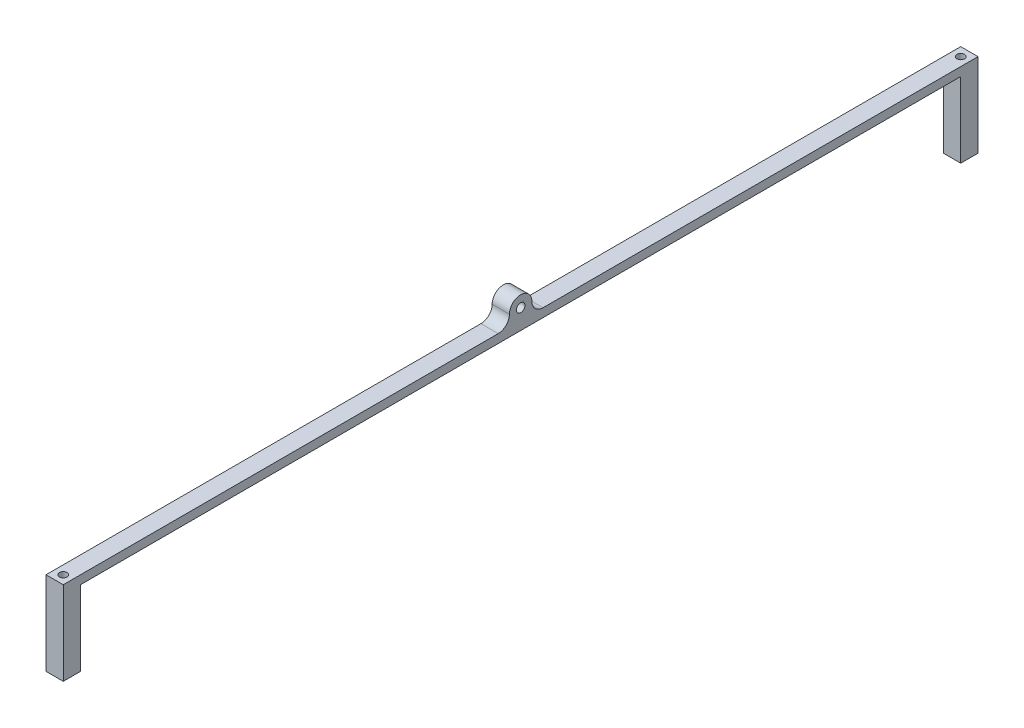
SolidWorks part; units mm, degrees
ref_plane "Спереди" through (0, 0, 0) normal (0, 0, 1) x (1, 0, 0)
ref_plane "Сверху" through (0, 0, 0) normal (0, 1, 0) x (1, 0, 0)
ref_plane "Справа" through (0, 0, 0) normal (1, 0, 0) x (0, 0, -1)
other "Configuration Table"
sketch "Эскиз1" plane through (0, 0, 0) normal (0, 1, 0) x (1, 0, 0)
  line L1 (0, 530) -> (10, 530)
  line L2 (0, 530) -> (0, 0)
  line L3 (0, 0) -> (10, 0)
  line L4 (10, 530) -> (10, 0)
  line L5 (592.3, 530) -> (592.3, 0) construction
  line L7 (0, 520) -> (10, 530) construction
  line L10 (0, 520) -> (10, 520) construction
  line L14 (0, 10) -> (10, 10) construction
  line L16 (0, 530) -> (10, 520) construction
  line L17 (0, 10) -> (10, 0) construction
  line L18 (10, 10) -> (0, 0) construction
  circle A0 centre (5, 525) radius 2.25
  circle A1 centre (5, 5) radius 2.25
  point P6 (10, 0)
  point P7 (0, 0)
  point P8 (0, 0)
  point P9 (10, 0)
  point P18 (10, 520)
  point P19 (0, 0)
  point P20 (-28.9465, 555.6129)
  point P21 (5, 525)
  point P22 (0, 0)
  point P23 (5, 5)
  point P25 (0, 0)
  point P26 (0, 0)
  point P27 (0, 0)
  point P28 (3.9913, 1.0186)
  point P29 (0, 0)
  point P31 (0, 0)
  point P32 (0, 0)
  point P34 (0, 10)
  dimension "D5" = 4.5
  dimension "D6" = 4.5
  dimension "D2" = 10
  dimension "D3" = 10
  dimension "D4" = 10
extrude "Бобышка-Вытянуть1" add sketch "Эскиз1" along normal blind 5
sketch "Эскиз2" plane through (0, 0, 0) normal (1, 0, 0) x (0, 0, -1)
  line L0 (258.5, 11.5) -> (271.5, 11.5) construction
  line L1 (252, 5) -> (278, 5)
  line L2 (0, 5) -> (530, 5) construction
  arc A0 (271.5, 11.5) -> (258.5, 11.5) centre (265, 11.5) ccw
  arc A2 (252, 5) -> (258.5, 11.5) centre (252, 11.5) ccw
  arc A3 (271.5, 11.5) -> (278, 5) centre (278, 11.5) ccw
  circle A4 centre (265, 11.5) radius 2.5
  point P1 (265, 5)
  point P5 (265, 5)
  point P6 (271.5, 11.5)
  point P7 (258.5, 11.5)
  dimension "D1" = 13
  dimension "D2" = 13
  dimension "D3" = 13
  dimension "D4" = 5
extrude "Бобышка-Вытянуть2" add sketch "Эскиз2" along normal blind 10
sketch "Эскиз3" plane through (0, 0, 0) normal (0, -1, 0) x (1, 0, 0)
  line L0 (10, 0) -> (10, -530) construction
  line L1 (0, 0) -> (10, 0)
  line L2 (0, 0) -> (0, -10)
  line L3 (0, -10) -> (10, -10)
  line L4 (10, 0) -> (10, -10)
  line L6 (0, -530) -> (10, -530)
  line L7 (0, -530) -> (0, -520)
  line L8 (0, -520) -> (10, -520)
  line L9 (10, -530) -> (10, -520)
  circle A526 centre (5, -525) radius 2.25
  circle A527 centre (5, -525) radius 2.25
  circle A529 centre (5, -5) radius 2.25
  circle A530 centre (5, -5) radius 2.25
  dimension "D1" = 10
  dimension "D2" = 10
  dimension "D3" = 0
  dimension "D4" = 0
extrude "Бобышка-Вытянуть3" add sketch "Эскиз3" along normal up to surface (43.5 mm away)
